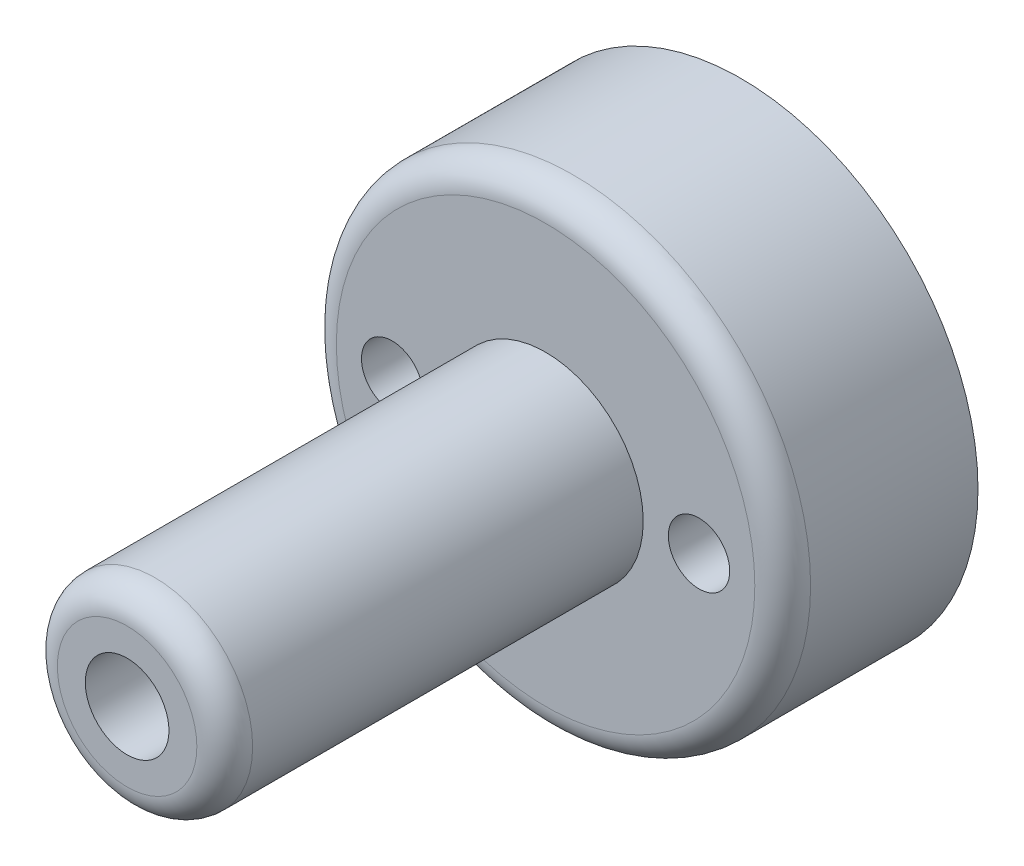
SolidWorks part; units mm, degrees
ref_plane "Front Plane" through (0, 0, 0) normal (0, 0, 1) x (1, 0, 0)
ref_plane "Top Plane" through (0, 0, 0) normal (0, 1, 0) x (1, 0, 0)
ref_plane "Right Plane" through (0, 0, 0) normal (1, 0, 0) x (0, 0, -1)
sketch "Sketch1" plane through (0, 0, 0) normal (0, 0, 1) x (1, 0, 0)
  circle A0 centre (0, 0) radius 7.55
  circle A1 centre (0, 0) radius 8.5
  dimension "D1" = 15.1
  dimension "D2" = 17
extrude "Boss-Extrude1" add sketch "Sketch1" along normal blind 5
sketch "Sketch2" plane through (0, 0, 5) normal (0, 0, 1) x (1, 0, 0)
  circle A0 centre (0, 0) radius 8.5 construction
  circle A1 centre (0, 0) radius 8.5
  circle A2 centre (0, 0) radius 1.1
  dimension "D1" = 2.2
extrude "Boss-Extrude2" add sketch "Sketch2" along normal blind 2
sketch "Sketch3" plane through (0, 0, 7) normal (0, 0, 1) x (1, 0, 0)
  circle A0 centre (-5.5, 0) radius 1.1
  circle A1 centre (5.5, 0) radius 1.1
  circle A2 centre (0, 0) radius 1.1 construction
  circle A3 centre (0, 0) radius 1.5
  circle A4 centre (0, 0) radius 3.5
  dimension "D1" = 5.5
  dimension "D3" = 3
  dimension "D4" = 7
  dimension "D2" = 5.5
extrude "Boss-Extrude3" add sketch "Sketch3" along normal blind 15 contours A4 A3 region at (-3.401, 0, 7)
extrude "Cut-Extrude1" cut sketch "Sketch3<3>" against normal through all both and the other way through all contours A0 | A1 region at (-5.5, 0, 7)
sketch "Sketch3<3>" plane through (0, 0, 7) normal (0, 0, 1) x (1, 0, 0) same geometry as "Sketch3"
sketch "Sketch4" plane through (0, 0, 5) normal (0, 0, -1) x (-1, 0, 0)
  circle A0 centre (-5.5, 0) radius 1.1 construction
  circle A1 centre (5.5, 0) radius 1.1 construction
  circle A2 centre (0, 0) radius 1.1 construction
  circle A3 centre (-5.5, 0) radius 1.1
  circle A4 centre (5.5, 0) radius 1.1
  circle A5 centre (0, 0) radius 1.1
  circle A6 centre (5.5, 0) radius 1.6
  circle A7 centre (0, 0) radius 1.6
  circle A8 centre (-5.5, 0) radius 1.6
  dimension "D1" = 0.5
extrude "Boss-Extrude4" add sketch "Sketch4" along normal up to surface (5 mm away) up to face at (8.5, 0, 0)
sketch "Sketch5" plane through (0, 0, 5) normal (0, 0, -1) x (-1, 0, 0)
  circle A0 centre (5.5, 0) radius 1.1 construction
  circle A1 centre (-5.5, 0) radius 1.1 construction
  circle A2 centre (0, 0) radius 1.1 construction
  circle A3 centre (5.5, 0) radius 1.1
  circle A4 centre (-5.5, 0) radius 1.1
  circle A5 centre (0, 0) radius 1.1
extrude "Boss-Extrude5" add sketch "Sketch5" against normal blind 0.3
fillet "Fillet1" radius 1 2 edges at (3.5, 0, 22) (8.5, 0, 7)
